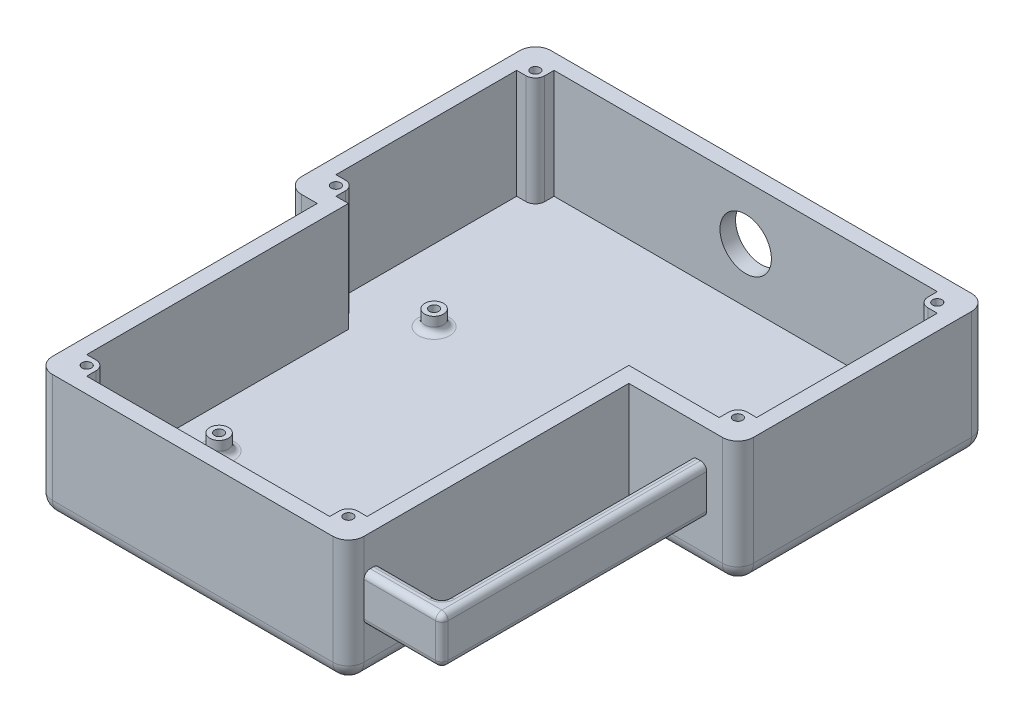
SolidWorks part; units mm, degrees
ref_plane "Front Plane" through (0, 0, 0) normal (0, 0, 1) x (1, 0, 0)
ref_plane "Top Plane" through (0, 0, 0) normal (0, 1, 0) x (1, 0, 0)
ref_plane "Right Plane" through (0, 0, 0) normal (1, 0, 0) x (0, 0, -1)
sketch "Sketch1" plane through (0, 0, 0) normal (0, 1, 0) x (1, 0, 0)
  line L0 (45, 50) -> (60, 50)
  line L2 (-50, 45) -> (-50, -45)
  line L3 (-50, -45) -> (50, -45)
  line L4 (50, 45) -> (50, -45)
  line L5 (-50, 45) -> (50, -45) construction
  line L6 (-50, -45) -> (50, 45) construction
  line L7 (60, 50) -> (80, 50)
  line L8 (-60, 125) -> (60, 125)
  line L9 (-60, 125) -> (-60, 45)
  line L10 (-60, 45) -> (-50, 45)
  line L12 (-60, 125) -> (60, 45) construction
  line L13 (-60, 45) -> (60, 125) construction
  line L14 (60, 125) -> (80, 125)
  line L16 (60, 45) -> (80, 45)
  line L17 (85, 120) -> (85, 50)
  line L22 (50, 45) -> (60, 45)
  line L23 (80, 120) -> (80, 50)
  line L24 (60, 120) -> (80, 120)
  line L29 (-55, 120) -> (60, 120)
  line L30 (-55, 120) -> (-55, 50)
  line L31 (-55, 50) -> (-45, 50)
  line L32 (-45, 50) -> (-45, -40)
  line L33 (-45, -40) -> (45, -40)
  line L34 (45, 50) -> (45, -40)
  arc A0 (80, 45) -> (85, 50) centre (80, 50) ccw
  arc A1 (80, 125) -> (85, 120) centre (80, 120) cw
  arc A4 (80, 50) -> (80, 50) centre (80, 50) ccw
  arc A5 (80, 120) -> (80, 120) centre (80, 120) cw
  point P0 (0, 0)
  point P22 (85, 45)
  dimension "D8" = 5
  dimension "D1" = 100
  dimension "D2" = 90
  dimension "D3" = 5
  dimension "D4" = 120
  dimension "D5" = 35
  dimension "D6" = 80
extrude "Boss-Extrude1" add sketch "Sketch1" along normal blind 35 contours L4 L2 L3 | L8 L9 L10 A5 | L17 L14 L16 region at (-55, 0, -47.2344)
sketch "Sketch7" plane through (0, 0, 0) normal (0, -1, 0) x (1, 0, 0)
  line L11 (-60, -45) -> (80, -45)
  line L12 (-60, -45) -> (-60, -125)
  line L13 (-60, -125) -> (80, -125)
  line L14 (85, -50) -> (85, -120)
  line L15 (-50, 45) -> (50, 45)
  line L16 (-50, 45) -> (-50, -45)
  line L17 (-50, -45) -> (50, -45)
  line L18 (50, 45) -> (50, -45)
  arc A2 (80, -125) -> (85, -120) centre (80, -120) ccw
  arc A3 (80, -45) -> (85, -50) centre (80, -50) cw
  point P12 (85, -125)
  point P15 (85, -45)
  dimension "D1" = 80
  dimension "D5" = 5
  dimension "D2" = 145
  dimension "D3" = 90
  dimension "D4" = 100
extrude "Boss-Extrude4" add sketch "Sketch7" along normal blind 5 contours L11 A3 L14 A2 L13 L12 | L16 L15 L18 L17
fillet "Fillet4" radius 5 13 edges at (-60, 15, -45) (-50, 15, 45) (50, 15, 45) (-60, 15, -125) (65, -5, -45) (83.5355, -5, -46.4645) (10, -5, -125) (83.5355, -5, -123.5355) (85, -5, -85) (-60, -5, -85) (-50, -5, 0) (0, -5, 45) (50, -5, 0)
sketch "Sketch8" plane through (0, 0, 0) normal (0, 1, 0) x (1, 0, 0)
  line L0 (-45, 5) -> (45, 5) construction
  line L1 (-45, 50) -> (-45, -40) construction
  line L2 (45, 50) -> (45, -40) construction
  line L3 (12.5, 120) -> (12.5, 5) construction
  line L4 (-55, 120) -> (80, 120) construction
  line L5 (-55, 85) -> (80, 85) construction
  line L6 (-55, 120) -> (-55, 50) construction
  line L7 (80, 120) -> (80, 50) construction
  line L8 (0, 5) -> (0, -40) construction
  line L9 (-45, -40) -> (45, -40) construction
  line L10 (-45, -37) -> (-39, -37) construction
  line L11 (-45, -40) -> (-39, -40)
  line L12 (-45, -40) -> (-45, -34)
  line L13 (-45, -34) -> (-39, -34)
  line L14 (-39, -40) -> (-39, -34)
  line L15 (-45, -40) -> (-39, -40)
  line L16 (-45, -34) -> (-39, -34)
  line L17 (45, -37) -> (39, -37) construction
  line L18 (45, -34) -> (39, -34)
  line L19 (45, -40) -> (39, -40)
  line L20 (39, -40) -> (39, -34)
  line L21 (45, -34) -> (39, -34)
  line L22 (45, -40) -> (45, -34)
  line L23 (45, -40) -> (39, -40)
  line L24 (-55, 120) -> (-55, 114)
  line L25 (-52, 50) -> (-52, 56) construction
  line L38 (-52, 120) -> (-52, 114) construction
  line L39 (-55, 120) -> (-49, 120)
  line L40 (-55, 120) -> (-55, 114)
  line L41 (-55, 114) -> (-49, 114)
  line L42 (-49, 120) -> (-49, 114)
  line L43 (-55, 120) -> (-55, 114)
  line L44 (-49, 120) -> (-49, 114)
  line L45 (-55, 120) -> (-55, 114)
  line L46 (-49, 120) -> (-49, 114)
  line L47 (-55, 120) -> (-55, 114)
  line L52 (-49, 120) -> (-49, 114)
  line L53 (-55, 120) -> (-55, 114)
  line L54 (-49, 120) -> (-49, 114)
  line L55 (-55, 120) -> (-55, 114)
  line L56 (-49, 120) -> (-49, 114)
  line L57 (-55, 120) -> (-55, 114)
  line L58 (-49, 120) -> (-49, 114)
  line L59 (-55, 120) -> (-55, 114)
  line L60 (-49, 120) -> (-49, 114)
  line L63 (-49, 120) -> (-49, 114)
  line L64 (-55, 120) -> (-55, 114)
  line L65 (-49, 120) -> (-49, 114)
  line L66 (-55, 120) -> (-55, 114)
  line L67 (-49, 120) -> (-49, 114)
  line L68 (-55, 120) -> (-55, 114)
  line L69 (-49, 120) -> (-49, 114)
  line L70 (-55, 120) -> (-55, 114)
  line L71 (-49, 120) -> (-49, 114)
  line L72 (-55, 120) -> (-55, 114)
  line L73 (-49, 120) -> (-49, 114)
  line L74 (-55, 120) -> (-55, 114)
  line L75 (-49, 120) -> (-49, 114)
  line L80 (-55, 120) -> (-55, 114)
  line L81 (-49, 120) -> (-49, 114)
  line L82 (-55, 120) -> (-55, 114)
  line L87 (-49, 120) -> (-49, 114)
  line L92 (-49, 50) -> (-49, 56)
  line L93 (-55, 50) -> (-55, 56)
  line L94 (-49, 50) -> (-49, 56)
  line L95 (-55, 50) -> (-55, 56)
  line L96 (-49, 50) -> (-49, 56)
  line L97 (-55, 50) -> (-55, 56)
  line L98 (-49, 50) -> (-49, 56)
  line L99 (-55, 50) -> (-55, 56)
  line L100 (-49, 50) -> (-49, 56)
  line L101 (-55, 50) -> (-55, 56)
  line L102 (-49, 50) -> (-49, 56)
  line L103 (-55, 50) -> (-55, 56)
  line L104 (-49, 50) -> (-49, 56)
  line L105 (-55, 50) -> (-55, 56)
  line L106 (-49, 50) -> (-49, 56)
  line L107 (-55, 56) -> (-49, 56)
  line L108 (-55, 50) -> (-55, 56)
  line L109 (-55, 50) -> (-49, 50)
  line L110 (-55, 120) -> (-55, 114)
  line L111 (-49, 120) -> (-49, 114)
  line L112 (-55, 120) -> (-55, 114)
  line L113 (-49, 120) -> (-49, 114)
  line L114 (-55, 120) -> (-55, 114)
  line L115 (-49, 120) -> (-49, 114)
  line L116 (-55, 120) -> (-55, 114)
  line L117 (-49, 120) -> (-49, 114)
  line L118 (-55, 120) -> (-55, 114)
  line L119 (-49, 120) -> (-49, 114)
  line L120 (-55, 120) -> (-55, 114)
  line L121 (-49, 120) -> (-49, 114)
  line L122 (-55, 120) -> (-55, 114)
  line L123 (-55, 120) -> (-55, 114)
  line L124 (-49, 120) -> (-49, 114)
  line L125 (-55, 120) -> (-55, 114)
  line L126 (-49, 120) -> (-49, 114)
  line L127 (-55, 120) -> (-55, 114)
  line L128 (-49, 120) -> (-49, 114)
  line L129 (-55, 120) -> (-55, 114)
  line L130 (-49, 120) -> (-49, 114)
  line L131 (-55, 120) -> (-55, 114)
  line L132 (-49, 120) -> (-49, 114)
  line L133 (-55, 120) -> (-55, 114)
  line L134 (-49, 120) -> (-49, 114)
  line L135 (-55, 120) -> (-55, 114)
  line L136 (-49, 120) -> (-49, 114)
  line L137 (-55, 120) -> (-55, 114)
  line L138 (-49, 120) -> (-49, 114)
  line L139 (-49, 120) -> (-49, 114)
  line L140 (77, 120) -> (77, 114) construction
  line L141 (80, 120) -> (74, 120)
  line L142 (80, 120) -> (80, 114)
  line L143 (80, 114) -> (74, 114)
  line L144 (74, 120) -> (74, 114)
  line L145 (80, 120) -> (80, 114)
  line L146 (74, 120) -> (74, 114)
  line L147 (77, 50) -> (77, 56) construction
  line L148 (74, 50) -> (74, 56)
  line L149 (80, 50) -> (80, 56)
  line L150 (74, 50) -> (74, 56)
  line L151 (80, 56) -> (74, 56)
  line L152 (80, 50) -> (80, 56)
  line L153 (80, 50) -> (74, 50)
  circle A0 centre (-42, -37) radius 1.5
  circle A1 centre (-42, -37) radius 3
  circle A2 centre (42, -37) radius 3
  circle A3 centre (42, -37) radius 1.5
  circle A8 centre (-52, 117) radius 3
  circle A10 centre (-52, 117) radius 1.5
  circle A15 centre (-52, 53) radius 1.5
  circle A16 centre (-52, 53) radius 3
  circle A19 centre (77, 117) radius 3
  circle A20 centre (77, 117) radius 1.5
  circle A21 centre (77, 53) radius 1.5
  circle A22 centre (77, 53) radius 3
  line M4 (80, 120) -> (-55, 120)
  line M5 (-55, 120) -> (-55, 50)
  line M6 (-55, 50) -> (-45, 50)
  line M7 (-45, 50) -> (-45, -40)
  line M8 (-45, -40) -> (45, -40)
  line M9 (45, -40) -> (45, 50)
  line M10 (45, 50) -> (80, 50)
  line M12 (80, 50) -> (80, 120)
  dimension "D3" = 3
  dimension "D6" = 3
  dimension "D9" = 3
  dimension "D1" = 6
  dimension "D2" = 6
  dimension "D4" = 6
  dimension "D5" = 6
  dimension "D7" = 6
  dimension "D8" = 6
extrude "Boss-Extrude5" add sketch "Sketch8" along normal blind 35 contours A1 L13 M7 | A1 A0 | A1 L12 M8 | A1 L15 L14 | A2 A3 | L18 A2 L22 | A2 L23 M9 | A2 L20 M8 | A16 L107 M5 | A16 A15 | A16 L108 M6 | L92 A16 L109 | A8 L59 L41 | A8 A10 | A8 L39 M5 | A8 L42 M4 | A19 L141 L144 | A19 A20 | A19 L145 M4 | A19 L143 M12 | A22 A21 | L151 A22 L152 | A22 L153 M12 | A22 L148 M10 region at (-44.3299, 0, 39.3299) region at (-39.6701, 0, 39.3299) region at (-44.0613, 0, 39.0613) region at (-44.3299, 0, 34.6701) region at (39.6701, 0, 39.3299) region at (44.3299, 0, 39.3299) region at (39.9387, 0, 39.0613) region at (-49.6701, 0, -50.6701) region at (44.3299, 0, 34.6701) region at (-49.9387, 0, -50.9387) region at (-54.3299, 0, -50.6701) region at (-54.3299, 0, -55.3299) region at (74.6701, 0, -50.6701) region at (-54.3299, 0, -114.6701) region at (74.9387, 0, -55.0613) region at (79.3299, 0, -50.6701) region at (-54.3299, 0, -119.3299) region at (-54.0613, 0, -119.0613) region at (79.3299, 0, -55.3299) region at (-49.6701, 0, -119.3299) region at (79.3299, 0, -114.6701) region at (74.6701, 0, -119.3299) region at (79.3299, 0, -119.3299) region at (79.0613, 0, -114.9387)
sketch "Sketch9" plane through (0, 0, 0) normal (0, 1, 0) x (1, 0, 0)
  line L0 (-35, 30) -> (35, 30) construction
  line L3 (0, 67.5) -> (0, -7.5) construction
  line L4 (-35, 67.5) -> (35, 67.5)
  line L5 (-35, 67.5) -> (-35, -7.5)
  line L6 (-35, -7.5) -> (35, -7.5)
  line L7 (35, 67.5) -> (35, -7.5)
  line L8 (-35, 67.5) -> (35, -7.5) construction
  line L9 (-35, -7.5) -> (35, 67.5) construction
  line L10 (-39, -40) -> (39, -40) construction
  circle A0 centre (-32, -4.5) radius 3
  circle A1 centre (-32, -4.5) radius 1.5
  circle A2 centre (32, -4.5) radius 1.5
  circle A3 centre (32, -4.5) radius 3
  circle A8 centre (32, 64.5) radius 3
  circle A9 centre (32, 64.5) radius 1.5
  circle A10 centre (-32, 64.5) radius 1.5
  circle A11 centre (-32, 64.5) radius 3
  point P6 (0, 30)
  point P23 (0, -40)
  dimension "D3" = 6
  dimension "D6" = 3
  dimension "D1" = 70
  dimension "D2" = 75
  dimension "D4" = 3
  dimension "D5" = 3
extrude "Boss-Extrude6" add sketch "Sketch9" along normal blind 5 contours A0 A1 | A3 A2 | A8 A9 | A11 A10 region at (-29.9387, 0, -66.5613) region at (34.0613, 0, -66.5613) region at (-32, 0, 1.5849) region at (34.0613, 0, 6.5613)
fillet "Fillet5" radius 2 4 edges at (32, 0, 7.5) (-32, 0, 1.5) (32, 0, -67.5) (-32, 0, -61.5)
sketch "Sketch10" plane through (0, 0, -125) normal (0, 0, -1) x (-1, 0, 0)
  line L0 (-80, 17.5) -> (55, 17.5) construction
  line L1 (-80, 35) -> (-80, 0) construction
  line L2 (55, 0) -> (55, 35) construction
  circle A0 centre (-12.5, 17.5) radius 8.25
  dimension "D1" = 16.5
extrude "Cut-Extrude1" cut sketch "Sketch10" against normal blind 10
sketch "Sketch11" plane through (50, 0, 0) normal (1, 0, 0) x (0, 0, -1)
  line L0 (-40, 17.5) -> (45, 17.5) construction
  line L1 (-40, 35) -> (-40, 0) construction
  line L2 (45, 35) -> (45, 0) construction
  line L4 (-40, 25) -> (45, 25)
  line L5 (-40, 25) -> (-40, 10)
  line L6 (-40, 10) -> (45, 10)
  line L7 (45, 25) -> (45, 10)
  line L8 (-40, 25) -> (45, 10) construction
  line L9 (-40, 10) -> (45, 25) construction
  point P6 (2.5, 17.5)
  dimension "D1" = 15
  dimension "D2" = 85
extrude "Boss-Extrude7" add sketch "Sketch11" along normal blind 25
sketch "Sketch12" plane through (0, 25, 0) normal (0, 1, 0) x (1, 0, 0)
  line L1 (50, 45) -> (75, 45)
  line L2 (50, 45) -> (50, -40)
  line L3 (50, -40) -> (75, -40)
  line L4 (75, 45) -> (75, -40)
  line L5 (50, 45) -> (70, 45)
  line L6 (50, 45) -> (50, -35)
  line L7 (50, -35) -> (70, -35)
  line L8 (70, 45) -> (70, -35)
  line M8 (50, 45) -> (50, -40)
  dimension "D4" = 20
  dimension "D1" = 85
  dimension "D2" = 25
  dimension "D3" = 80
extrude "Cut-Extrude2" cut sketch "Sketch12" against normal up to next contours L8 L1 L7 M8 region at (60, 25, -5)
fillet "Fillet6" radius 2 10 edges at (70, 10, -5) (60, 10, 35) (70, 17.5, 35) (70, 25, -5) (60, 25, 35) (75, 10, -2.5) (62.5, 10, 40) (75, 25, -2.5) (62.5, 25, 40) (75, 17.5, 40)
